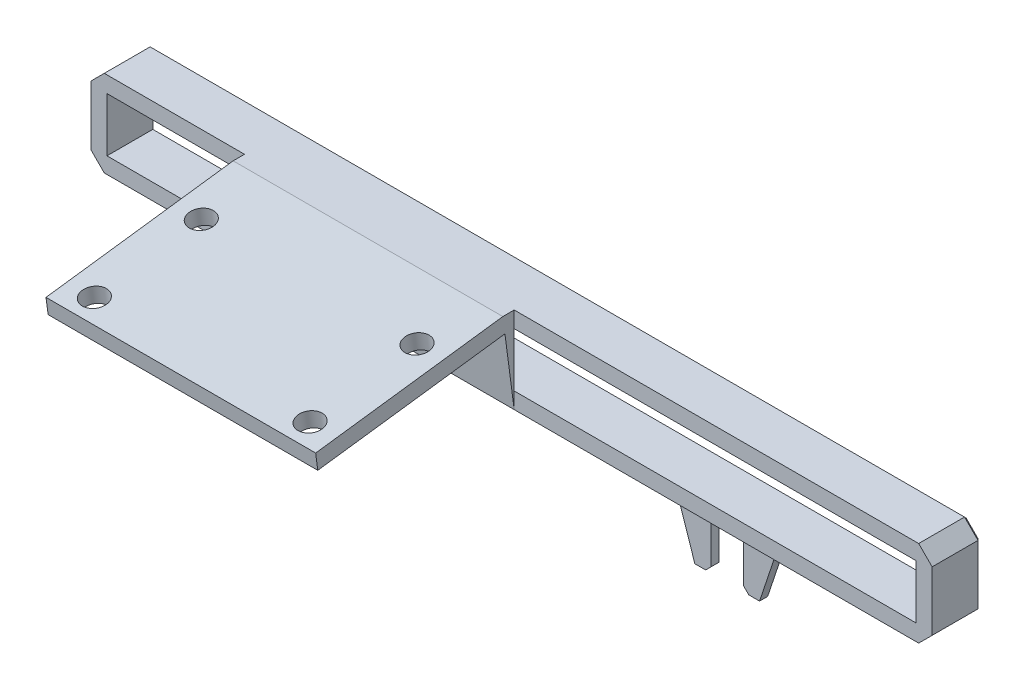
SolidWorks part; units mm, degrees
ref_plane "Top Plane" through (0, 0, 0) normal (0, 0, 1) x (1, 0, 0)
ref_plane "Front Plane" through (0, 0, 0) normal (0, 1, 0) x (1, 0, 0)
ref_plane "Right Plane" through (0, 0, 0) normal (1, 0, 0) x (0, 0, -1)
sketch "Sketch1" plane through (0, 0, 0) normal (0, 0, 1) x (1, 0, 0)
  line L1 (0, 0) -> (156, 0)
  line L2 (0, 0) -> (0, 16)
  line L3 (0, 16) -> (156, 16)
  line L4 (156, 0) -> (156, 16)
  dimension "D1" = 156
  dimension "D2" = 16
extrude "Boss-Extrude1" add sketch "Sketch1" along normal blind 9
sketch "Sketch2" plane through (0, 0, 9) normal (0, 0, 1) x (1, 0, 0)
  line L14 (153, 3) -> (153, 13)
  line L15 (3, 3) -> (153, 3)
  line L16 (3, 13) -> (3, 3)
  line L17 (153, 13) -> (3, 13)
  line L18 (153, 3) -> (153, 13)
  line L19 (3, 3) -> (153, 3)
  line L20 (3, 13) -> (3, 3)
  line L21 (153, 13) -> (3, 13)
  dimension "D1" = 3
extrude "Cut-Extrude1" cut sketch "Sketch2" against normal blind 9
sketch "Sketch4" plane through (156, 0, 0) normal (1, 0, 0) x (0, 0, -1)
  line L0 (-9, 16) -> (-11.1064, 16)
  line L1 (-11.1064, 16) -> (-9, 0)
  line L2 (-9, 0) -> (-9, 16)
  dimension "D1" = 7.5
extrude "Boss-Extrude2" add sketch "Sketch4" along normal blind 50 from offset 127.5 offset against normal yes
sketch "Sketch5" plane through (0, -1.1647, 8.8467) normal (0, -0.1305, 0.9914) x (1, 0, 0)
  line L0 (78.5, 17.3128) -> (78.5, 1.1747) construction
  line L1 (28.5, 17.3128) -> (78.5, 17.3128)
  line L2 (28.5, 17.3128) -> (28.5, 14.3128)
  line L3 (28.5, 14.3128) -> (78.5, 14.3128)
  line L4 (78.5, 17.3128) -> (78.5, 14.3128)
  line L6 (78.5, 17.3128) -> (28.5, 17.3128) construction
  line L7 (28.5, 17.3128) -> (28.5, 1.1747) construction
  dimension "D1" = 3
extrude "Boss-Extrude3" add sketch "Sketch5" along normal blind 35
sketch "Sketch6" plane through (0, 17.1647, 2.2598) normal (0, 0.9914, 0.1305) x (1, 0, 0)
  line L0 (78.5, -8.923) -> (28.5, -8.923) construction
  line L1 (33.5, -19.923) -> (73.5, -19.923)
  line L2 (33.5, -19.923) -> (33.5, -39.923)
  line L3 (33.5, -39.923) -> (73.5, -39.923)
  line L4 (73.5, -19.923) -> (73.5, -39.923)
  line L5 (28.5, -43.923) -> (28.5, -8.923) construction
  dimension "D1" = 40
  dimension "D2" = 20
  dimension "D3" = 11
  dimension "D4" = 5
hole_wizard "M4 Clearance Hole1" positions "Sketch7" profile "Sketch8" hole size "M4" standard "DIN" end condition through all
sketch "Sketch7" plane through (0, 17.1647, 2.2598) normal (0, 0.9914, 0.1305) x (1, 0, 0)
  point P0 (33.5, -19.923)
  point P3 (73.5, -19.923)
  point P6 (73.5, -39.923)
  point P9 (33.5, -39.923)
sketch "Sketch8" plane through (33.5, 14.5642, 22.0123) normal (1, 0, 0) x (0, -0.1305, 0.9914)
  line L0 (0, 0) -> (0, 17.3128)
  line L1 (0, 17.3128) -> (2.25, 17.3128)
  line L2 (2.25, 17.3128) -> (2.25, 0)
  line L5 (2.25, 0) -> (0, 0)
  line L11 (0, -6.35) -> (0, 107.95) construction
  dimension "Thru Hole Dia." = 4.5
  dimension "Thru Hole Depth" = 17.3128
sketch "Sketch10" plane through (0, 0, 0) normal (0, -1, 0) x (1, 0, 0)
  line L0 (0, 0) -> (156, 0) construction
  line L1 (105, 2) -> (117, 2)
  line L2 (105, 2) -> (105, 0)
  line L3 (105, 0) -> (117, 0)
  line L4 (117, 2) -> (117, 0)
  line L5 (156, 9) -> (156, 0) construction
  dimension "D1" = 2
  dimension "D2" = 12
  dimension "D3" = 39
extrude "Boss-Extrude4" add sketch "Sketch10" along normal blind 15
sketch "Sketch11" plane through (0, 0, 0) normal (0, 0, -1) x (-1, 0, 0)
  line L0 (-105, -15) -> (-117, -15) construction
  line L1 (-114, -15) -> (-108, -15)
  line L2 (-114, -15) -> (-114, -4)
  line L3 (-114, -4) -> (-108, -4)
  line L4 (-108, -15) -> (-108, -4)
  line L5 (0, 0) -> (-105, 0) construction
  line L6 (-105, -15) -> (-105, 0) construction
  dimension "D1" = 6
  dimension "D2" = 4
  dimension "D3" = 3
extrude "Cut-Extrude2" cut sketch "Sketch11" against normal blind 15
chamfer "Chamfer1" distance 5 distance2 15 2 edges at (117, 0, 1) (105, 0, 1) first distance on face at (86.3, 0, 4)
chamfer "Chamfer2" distance 1 angle 45 2 edges at (108, -15, 1) (114, -15, 1)
chamfer "Chamfer3" distance 2.5 angle 45 4 edges at (0, 0, 4.5) (0, 16, 4.5) (156, 16, 4.5) (156, 0, 4.5)
chamfer "Chamfer4" distance 2 angle 45 1 edges at (111, 0, 2)
chamfer "Chamfer5" distance 0.5 angle 45 22 edges at (3, 8, 0) (78, 13, 0) (153, 8, 0) (78, 3, 0) (102.5, -7.5, 0) (106, -15, 0) (107.5, -14.5, 0) (108, -9, 0) (111, -4, 0) (114, -9, 0) (114.5, -14.5, 0) (116, -15, 0) (119.5, -7.5, 0) (137.75, 0, 0) (154.75, 1.25, 0) (156, 8, 0) (154.75, 14.75, 0) (78, 16, 0) (1.25, 14.75, 0) (0, 8, 0) (1.25, 1.25, 0) (51.25, 0, 0)
ref_plane "Plane1" through (53.5, 0, 0) normal (-1, 0, 0) x (0, 0, 1)
